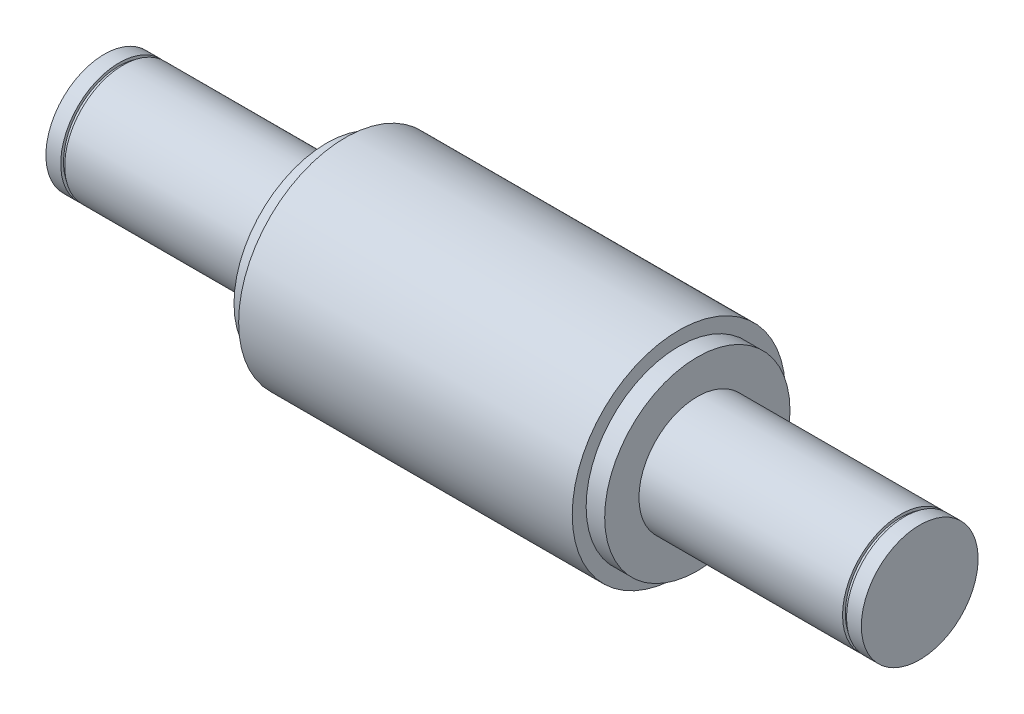
SolidWorks part; units mm, degrees
material "AISI 1020"
ref_plane "Ön Düzlem" through (0, 0, 0) normal (0, 0, 1) x (1, 0, 0)
ref_plane "Üst Düzlem" through (0, 0, 0) normal (0, 1, 0) x (1, 0, 0)
ref_plane "Sağ Düzlem" through (0, 0, 0) normal (1, 0, 0) x (0, 0, -1)
sketch "Çizim1" plane through (0, 0, 0) normal (1, 0, 0) x (0, 0, -1)
  circle A0 centre (0, 0) radius 57.5
  circle A1 centre (0, 0) radius 50
  dimension "D1" = 115
  dimension "D2" = 100
extrude "Yükseklik-Ekstrüzyon1" add sketch "Çizim1" along normal mid plane 200 contours A1 region at (0, 0, 0)
extrude "Yükseklik-Ekstrüzyon2" add sketch "Çizim1<3>" along normal mid plane 180
sketch "Çizim1<3>" plane through (0, 0, 0) normal (1, 0, 0) x (0, 0, -1) same geometry as "Çizim1"
sketch "Çizim11" plane through (100, 0, 0) normal (1, 0, 0) x (0, 0, -1)
  circle A0 centre (0, 0) radius 31.5
  dimension "D1" = 63
extrude "Yükseklik-Ekstrüzyon7" add sketch "Çizim11" along normal blind 120
sketch "Çizim12" plane through (0, 0, 0) normal (0, 0, 1) x (1, 0, 0)
  line L0 (209.85, 35.2305) -> (209.85, 30)
  line L1 (212, 30) -> (212, 35.2305)
  line L2 (212, 30) -> (209.85, 30)
  line L3 (220, 31.5) -> (100, 31.5) construction
  line L4 (212, 35.2305) -> (209.85, 35.2305)
  dimension "D1" = 2.15
  dimension "D2" = 8
  dimension "D3" = 1.5
revolve "Kes-Döndür1" cut sketch "Çizim12" angle 360 about axis through (220, 0, 0) along (-1, 0, 0) region at (210.925, 32.6152, 0)
mirror "Aynalama6" about plane through (0, 0, 0) normal (1, 0, 0) of "Kes-Döndür1", "Yükseklik-Ekstrüzyon7"
